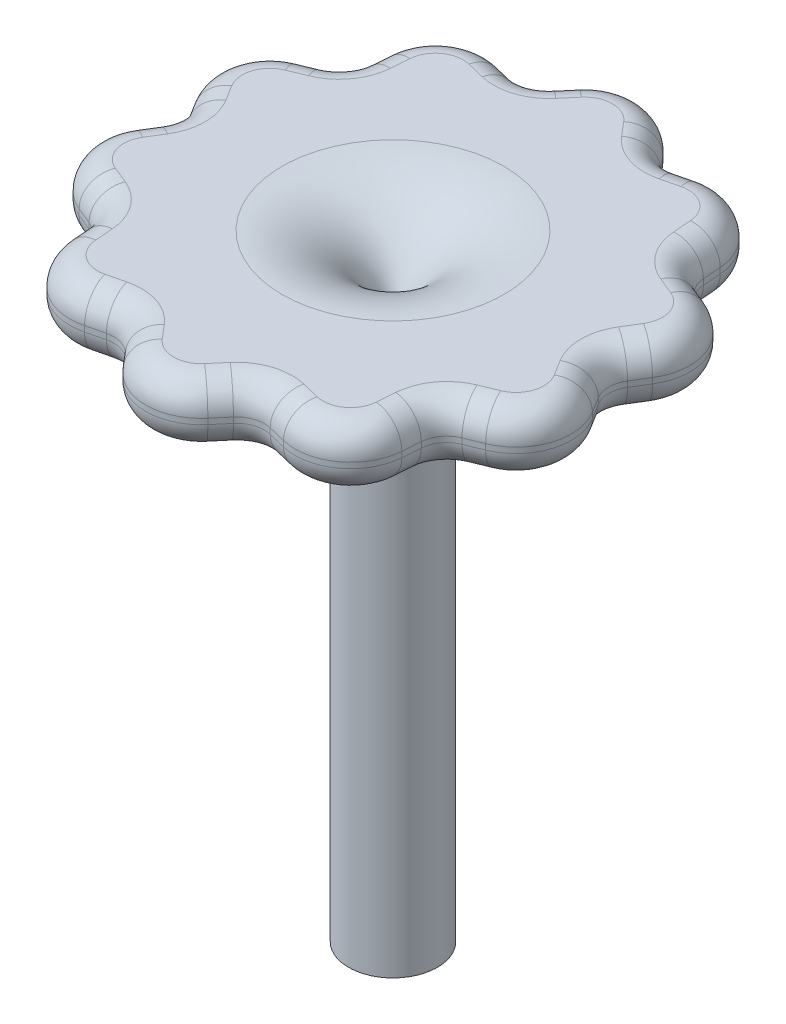
SolidWorks part; units mm, degrees
ref_plane "Front Plane" through (0, 0, 0) normal (0, 0, 1) x (1, 0, 0)
ref_plane "Top Plane" through (0, 0, 0) normal (0, 1, 0) x (1, 0, 0)
ref_plane "Right Plane" through (0, 0, 0) normal (1, 0, 0) x (0, 0, -1)
sketch "Sketch1" plane through (0, 0, 0) normal (0, 0, 1) x (1, 0, 0)
  line L0 (0, 0) -> (0, 91) construction
  line L1 (0, 0) -> (8, 0)
  line L2 (8, 0) -> (8, 80)
  line L3 (28, 100) -> (45, 100)
  line L4 (50, 105) -> (50, 106)
  line L5 (45, 111) -> (20, 111)
  line L6 (0, 0) -> (0, 91)
  arc A0 (8, 80) -> (28, 100) centre (28, 80) cw
  arc A1 (0, 91) -> (20, 111) centre (20, 91) cw
  arc A2 (45, 100) -> (50, 105) centre (45, 105) ccw
  arc A3 (50, 106) -> (45, 111) centre (45, 106) ccw
  point P10 (8, 100)
  dimension "D3" = 20
  dimension "D1" = 20
  dimension "D7" = 5
  dimension "D2" = 100
  dimension "D4" = 100
  dimension "D5" = 16
  dimension "D6" = 11
revolve "Revolve1" add sketch "Sketch1" angle 360 about L0
sketch "Sketch2" plane through (0, 111, 0) normal (0, 1, 0) x (1, 0, 0)
  line L0 (0, -50) -> (0, 0) construction
  line L1 (-29.3893, -40.4508) -> (0, 0) construction
  line L2 (-47.5528, -15.4508) -> (0, 0) construction
  line L3 (-47.5528, 15.4508) -> (0, 0) construction
  line L4 (-29.3893, 40.4508) -> (0, 0) construction
  line L5 (0, 50) -> (0, 0) construction
  line L6 (29.3893, 40.4508) -> (0, 0) construction
  line L7 (47.5528, 15.4508) -> (0, 0) construction
  line L8 (47.5528, -15.4508) -> (0, 0) construction
  line L9 (29.3893, -40.4508) -> (0, 0) construction
  line L10 (-29.3893, -40.4508) -> (-30.7426, -22.3358)
  line L11 (-30.7426, -22.3358) -> (-47.5528, -15.4508)
  line L12 (-47.5528, -15.4508) -> (-38, 0)
  line L13 (-38, 0) -> (-47.5528, 15.4508)
  line L14 (-47.5528, 15.4508) -> (-30.7426, 22.3358)
  line L15 (-30.7426, 22.3358) -> (-29.3893, 40.4508)
  line L16 (-29.3893, 40.4508) -> (-11.7426, 36.1401)
  line L17 (-11.7426, 36.1401) -> (0, 50)
  line L18 (0, 50) -> (11.7426, 36.1401)
  line L19 (11.7426, 36.1401) -> (29.3893, 40.4508)
  line L20 (29.3893, 40.4508) -> (30.7426, 22.3358)
  line L21 (30.7426, 22.3358) -> (47.5528, 15.4508)
  line L22 (47.5528, 15.4508) -> (38, 0)
  line L23 (38, 0) -> (47.5528, -15.4508)
  line L24 (47.5528, -15.4508) -> (30.7426, -22.3358)
  line L25 (30.7426, -22.3358) -> (29.3893, -40.4508)
  line L26 (29.3893, -40.4508) -> (11.7426, -36.1401)
  line L27 (11.7426, -36.1401) -> (0, -50)
  line L28 (0, -50) -> (-11.7426, -36.1401)
  line L29 (-11.7426, -36.1401) -> (-29.3893, -40.4508)
  line L30 (-30.7426, -22.3358) -> (0, 0) construction
  circle A2 centre (0, 0) radius 50 construction
  point P25 (0, 0)
  dimension "D1" = 10
extrude "Extrude1" cut sketch "Sketch2" against normal blind 40 flip side to cut
fillet "Congé1" radius 10 1 edges at (-47.5528, 105.5, 15.4508) type face fillet first side face at (-40.4944, 105.3744, 18.3418) second side face at (-43.5417, 105.6256, 8.9632)
fillet "Congé2" radius 10 1 edges at (-29.3893, 105.5, 40.4508) type face fillet first side face at (-29.9575, 105.6256, 32.8445) second side face at (-21.9796, 105.3744, 38.6408)
fillet "Congé3" radius 10 1 edges at (0, 105.5, 50) type face fillet first side face at (-4.9306, 105.6256, 44.1804) second side face at (4.9306, 105.3744, 44.1804)
fillet "Congé4" radius 10 1 edges at (29.3893, 105.5, 40.4508) type face fillet first side face at (21.9796, 105.6256, 38.6408) second side face at (29.9575, 105.3744, 32.8445)
fillet "Congé5" radius 10 1 edges at (47.5528, 105.5, 15.4508) type face fillet first side face at (40.4944, 105.6256, 18.3418) second side face at (43.5417, 105.3744, 8.9632)
fillet "Congé6" radius 10 1 edges at (47.5528, 105.5, -15.4508) type face fillet first side face at (43.5417, 105.6256, -8.9632) second side face at (40.4944, 105.3744, -18.3418)
fillet "Congé7" radius 10 1 edges at (29.3893, 105.5, -40.4508) type face fillet first side face at (29.9575, 105.6256, -32.8445) second side face at (21.9796, 105.3744, -38.6408)
fillet "Congé8" radius 10 1 edges at (0, 105.5, -50) type face fillet first side face at (4.9306, 105.6256, -44.1804) second side face at (-4.9306, 105.3744, -44.1804)
fillet "Congé9" radius 10 1 edges at (-29.3893, 105.5, -40.4508) type face fillet first side face at (-21.9796, 105.6256, -38.6408) second side face at (-29.9575, 105.3744, -32.8445)
fillet "Congé10" radius 10 1 edges at (-47.5528, 105.5, -15.4508) type face fillet first side face at (-40.4944, 105.6256, -18.3418) second side face at (-43.5417, 105.3744, -8.9632)
fillet "Fillet1" radius 5 70 edges at (-9.6862, 100, 38.5674) (-9.6862, 111, 38.5674) (-14.833, 111, 36.8951) (-11.7426, 105.5, 36.1401) (-14.833, 100, 36.8951) (-30.5056, 100, 25.5082) (-30.5056, 111, 25.5082) (-33.6865, 111, 21.1301) (-30.7426, 105.5, 22.3358) (-33.6865, 100, 21.1301) (-39.6729, 100, 2.7058) (-39.6729, 111, 2.7058) (-39.6729, 111, -2.7058) (-38, 105.5, 0) (-39.6729, 100, -2.7058) (-33.6865, 100, -21.1301) (-33.6865, 111, -21.1301) (-30.5056, 111, -25.5082) (-30.7426, 105.5, -22.3358) (-30.5056, 100, -25.5082) (-14.833, 100, -36.8951) (-14.833, 111, -36.8951) (-9.6862, 111, -38.5674) (-11.7426, 105.5, -36.1401) (-9.6862, 100, -38.5674) (9.6862, 100, -38.5674) (9.6862, 111, -38.5674) (14.833, 111, -36.8951) (11.7426, 105.5, -36.1401) (14.833, 100, -36.8951) (30.5056, 100, -25.5082) (30.5056, 111, -25.5082) (33.6865, 111, -21.1301) (30.7426, 105.5, -22.3358) (33.6865, 100, -21.1301) (39.6729, 100, -2.7058) (39.6729, 111, -2.7058) (39.6729, 111, 2.7058) (38, 105.5, 0) (39.6729, 100, 2.7058) (33.6865, 100, 21.1301) (33.6865, 111, 21.1301) (30.5056, 111, 25.5082) (30.7426, 105.5, 22.3358) (30.5056, 100, 25.5082) (14.833, 100, 36.8951) (14.833, 111, 36.8951) (9.6862, 111, 38.5674) (11.7426, 105.5, 36.1401) (9.6862, 100, 38.5674) (-26.1743, 111, 36.0258) (-26.1743, 100, 36.0258) (-42.3509, 111, 13.7606) (-42.3509, 100, 13.7606) (-42.3509, 111, -13.7606) (-42.3509, 100, -13.7606) (-26.1743, 111, -36.0258) (-26.1743, 100, -36.0258) (0, 111, -44.5303) (0, 100, -44.5303) (26.1743, 111, -36.0258) (26.1743, 100, -36.0258) (42.3509, 111, -13.7606) (42.3509, 100, -13.7606) (42.3509, 111, 13.7606) (42.3509, 100, 13.7606) (26.1743, 111, 36.0258) (26.1743, 100, 36.0258) (0, 100, 44.5303) (0, 111, 44.5303)
